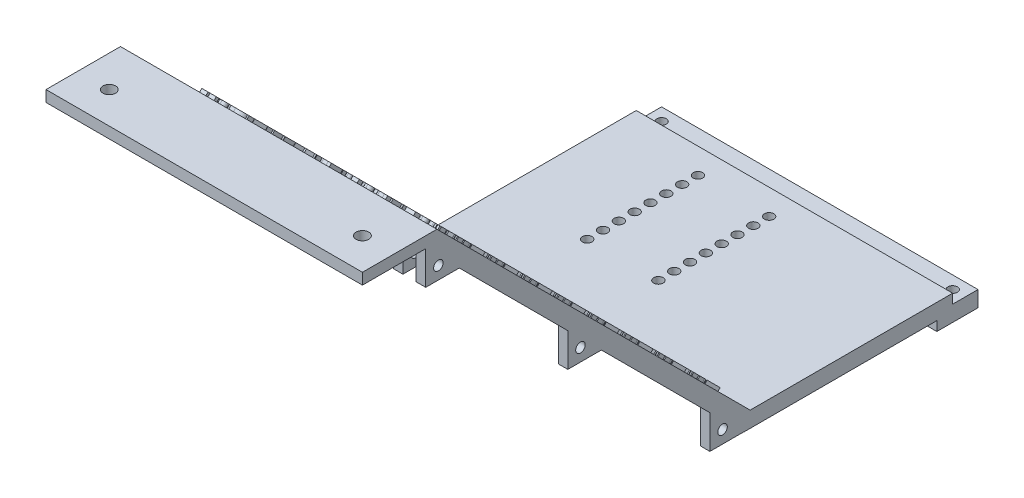
SolidWorks part; units mm, degrees
ref_plane "Front Plane" through (0, 0, 0) normal (0, 0, 1) x (1, 0, 0)
ref_plane "Top Plane" through (0, 0, 0) normal (0, 1, 0) x (1, 0, 0)
ref_plane "Right Plane" through (0, 0, 0) normal (1, 0, 0) x (0, 0, -1)
sketch "Sketch4" plane through (0, 0, 0) normal (1, 0, 0) x (0, 0, -1)
  line L0 (0, 0) -> (-8, 0)
  line L1 (-8, 0) -> (-8, 3)
  line L2 (-8, 3) -> (-72, 3)
  line L3 (-72, 3) -> (-170.9949, 101.9949)
  dimension "D1" = 8
  dimension "D2" = 3
  dimension "D3" = 64
  dimension "D4" = 135
  dimension "D5" = 140
extrude "Extrude-Thin2" add sketch "Sketch4" along normal blind 100 thin thin type one direction reverse wall 5
sketch "Sketch5" plane through (0, 3, 0) normal (0, 1, 0) x (1, 0, 0)
  line L1 (100, -8) -> (100, -72) construction
  line L2 (100, -8) -> (0, -8) construction
  circle A0 centre (50, -16) radius 1.5
  dimension "D2" = 3
  dimension "D1" = 50
  dimension "D3" = 8
extrude "Cut-Extrude1" cut sketch "Sketch5" against normal up to next
pattern_linear "LPattern1" count 8 spacing 5 along (0, 0, 1) count 2 spacing 22.5 along (-1, 0, 0) of "Cut-Extrude1"
sketch "Sketch7" plane through (100, 0, 0) normal (1, 0, 0) x (0, 0, -1)
  line L0 (-170.9949, 101.9949) -> (-174.5305, 101.9949)
  line L1 (-174.5305, 101.9949) -> (-174.5305, 98.4594)
  line L2 (-174.5305, 98.4594) -> (-170.9949, 101.9949)
extrude "Boss-Extrude1" add sketch "Sketch7" against normal up to surface (100 mm away) up to face at (0, 19.2454, 53.3597)
sketch "Sketch8" plane through (0, 0, 174.5305) normal (0, 0, 1) x (1, 0, 0)
  line L1 (0, 101.9949) -> (100, 101.9949)
  line L2 (0, 101.9949) -> (0, 98.4594)
  line L3 (0, 98.4594) -> (100, 98.4594)
  line L4 (100, 101.9949) -> (100, 98.4594)
extrude "Boss-Extrude2" add sketch "Sketch8" along normal blind 20
sketch "Sketch9" plane through (0, 101.9949, 0) normal (0, 1, 0) x (1, 0, 0)
  line L0 (100, -170.9949) -> (100, -194.5305) construction
  line L1 (100, -194.5305) -> (0, -194.5305) construction
  line L2 (0, -170.9949) -> (0, -194.5305) construction
  circle A0 centre (90, -184.5305) radius 2
  circle A1 centre (10, -184.5305) radius 2
  dimension "D1" = 4
  dimension "D2" = 4
  dimension "D3" = 10
  dimension "D4" = 10
  dimension "D5" = 10
  dimension "D6" = 10
extrude "Cut-Extrude2" cut sketch "Sketch9" against normal up to next
sketch "Sketch10" plane through (0, 0, 0) normal (0, 1, 0) x (1, 0, 0)
  line L0 (100, 0) -> (0, 0) construction
  line L1 (100, 0) -> (100, -8) construction
  line L2 (0, 0) -> (0, -8) construction
  circle A0 centre (4, -4) radius 1.5
  circle A1 centre (96, -4) radius 1.5
  dimension "D1" = 3
  dimension "D2" = 3
  dimension "D3" = 4
  dimension "D4" = 4
  dimension "D5" = 4
extrude "Cut-Extrude3" cut sketch "Sketch10" against normal up to next
sketch "Sketch11" plane through (100, 0, 0) normal (1, 0, 0) x (0, 0, -1)
  line L0 (-174.5305, 98.4594) -> (-174.5305, 87.8528)
  line L1 (-174.5305, 87.8528) -> (-163.9239, 87.8528)
  line L2 (-74.0711, -2) -> (-174.5305, 98.4594) construction
  line L3 (-174.5305, 98.4594) -> (-163.9239, 87.8528)
  dimension "D1" = 15
extrude "Boss-Extrude3" add sketch "Sketch11" against normal blind 3
sketch "Sketch12" plane through (100, 0, 0) normal (1, 0, 0) x (0, 0, -1)
  line L0 (-174.5305, 98.4594) -> (-174.5305, 87.8528) construction
  line L1 (-174.5305, 87.8528) -> (-163.9239, 87.8528) construction
  circle A0 centre (-170.5305, 91.8528) radius 1.5
  dimension "D1" = 3
  dimension "D2" = 4
  dimension "D3" = 4
extrude "Cut-Extrude4" cut sketch "Sketch12" against normal up to next
pattern_linear "LPattern2" count 3 spacing 63.5 along (0, -0.7071, -0.7071) count 2 spacing 97 along (-1, 0, 0) of "Boss-Extrude3", "Cut-Extrude4"
sketch "Sketch13" plane through (0, -2, 0) normal (0, -1, 0) x (1, 0, 0)
  line L0 (0, 13) -> (0, 74.0711) construction
  line L1 (0, 48.535) -> (3, 48.535)
  line L2 (0, 48.535) -> (0, 38.535)
  line L3 (0, 38.535) -> (3, 38.535)
  line L4 (3, 48.535) -> (3, 38.535)
  dimension "D1" = 3
  dimension "D2" = 10
  dimension "D3" = 25.535
extrude "Boss-Extrude4" add sketch "Sketch13" along normal blind 10
sketch "Sketch14" plane through (0, 0, 0) normal (-1, 0, 0) x (0, 0, 1)
  line L0 (38.535, -12) -> (38.535, -2) construction
  line L1 (48.535, -12) -> (38.535, -12) construction
  circle A0 centre (43.535, -7) radius 1.5
  dimension "D1" = 3
  dimension "D2" = 5
  dimension "D3" = 5
extrude "Cut-Extrude5" cut sketch "Sketch14" against normal up to next
sketch "Sketch15" plane through (0, -34.5, 34.5) normal (0, 0.7071, -0.7071) x (1, 0, 0)
  line L0 (100, -53.033) -> (100, -193.033) construction
  line L1 (100, -193.033) -> (0, -193.033) construction
  circle A0 centre (84, -176.233) radius 3.4
  circle A1 centre (84, -161.233) radius 3.4
  circle A2 centre (84, -146.233) radius 3.4
  circle A5 centre (84, -131.233) radius 3.4
  circle A6 centre (84, -116.233) radius 3.4
  circle A7 centre (84, -101.233) radius 3.4
  circle A8 centre (84, -86.233) radius 3.4
  circle A9 centre (84, -71.233) radius 3.4
  point P20 (0, 0)
  dimension "D1" = 6.8
  dimension "D2" = 6.8
  dimension "D3" = 6.8
  dimension "D8" = 6.8
  dimension "D9" = 6.8
  dimension "D10" = 6.8
  dimension "D11" = 6.8
  dimension "D16" = 6.8
  dimension "D4" = 16
  dimension "D5" = 16.8
  dimension "D6" = 15
  dimension "D7" = 15
  dimension "D12" = 15
  dimension "D13" = 15
  dimension "D14" = 15
  dimension "D15" = 15
  dimension "D17" = 15
extrude "Cut-Extrude6" cut sketch "Sketch15" against normal up to next
sketch "Sketch16" plane through (0, -34.5, 34.5) normal (0, 0.7071, -0.7071) x (1, 0, 0)
  circle A0 centre (59, -161.233) radius 3.4
  circle A1 centre (44, -161.233) radius 3.4
  circle A2 centre (29, -161.233) radius 3.4
  circle A3 centre (14, -161.233) radius 3.4
  circle A5 centre (84, -161.233) radius 3.4 construction
  circle A6 centre (66.5, -146.233) radius 3.4
  circle A7 centre (51.5, -146.233) radius 3.4
  circle A8 centre (36.5, -146.233) radius 3.4
  circle A9 centre (21.5, -146.233) radius 3.4
  circle A10 centre (6.5, -146.233) radius 3.4
  circle A12 centre (51.5, -131.233) radius 3.4
  circle A13 centre (36.5, -131.233) radius 3.4
  circle A14 centre (21.5, -131.233) radius 3.4
  dimension "D1" = 6.8
  dimension "D2" = 15
  dimension "D3" = 15
  dimension "D7" = 6.8
  dimension "D14" = 6.8
  dimension "D4" = 15
  dimension "D5" = 0
  dimension "D6" = 25
  dimension "D8" = 15
  dimension "D9" = 15
  dimension "D10" = 15
  dimension "D11" = 15
  dimension "D12" = 7.5
  dimension "D13" = 15
  dimension "D15" = 15
  dimension "D16" = 15
  dimension "D17" = 15
extrude "Cut-Extrude7" cut sketch "Sketch16" against normal up to next
sketch "Sketch17" plane through (0, -34.5, 34.5) normal (0, 0.7071, -0.7071) x (1, 0, 0)
  circle A0 centre (51.5, -111.233) radius 3.4
  circle A1 centre (36.5, -106.233) radius 3.4
  circle A2 centre (21.5, -111.233) radius 3.4
  circle A3 centre (36.5, -131.233) radius 3.4 construction
  circle A4 centre (84, -116.233) radius 3.4 construction
  dimension "D1" = 6.8
  dimension "D4" = 5
  dimension "D2" = 15
  dimension "D3" = 15
  dimension "D5" = 0
  dimension "D6" = 5
extrude "Cut-Extrude8" cut sketch "Sketch17" against normal up to next
pattern_linear "LPattern3" count 4 spacing 15 along (0, -0.7071, -0.7071) of "Cut-Extrude8"
ref_plane "Plane1" through (0, -34.5, 34.5) normal (0, 0.7071, -0.7071) x (-1, 0, 0)
sketch "Sketch19" plane through (0, -34.5, 34.5) normal (0, 0.7071, -0.7071) x (-1, 0, 0)
  circle A0 centre (-84, 176.233) radius 3.4 construction
  text T0 "SENDS" font "Century Gothic" height 5
  dimension "D1" = 10
  dimension "D2" = 8
extrude "Boss-Extrude5" add sketch "Sketch19" along normal blind 1
sketch "Sketch21" plane through (0, -34.5, 34.5) normal (0, 0.7071, -0.7071) x (-1, 0, 0)
  circle A0 centre (-59, 161.233) radius 3.4 construction
  circle A1 centre (-44, 161.233) radius 3.4 construction
  circle A2 centre (-29, 161.233) radius 3.4 construction
  circle A3 centre (-14, 161.233) radius 3.4 construction
  circle A4 centre (-36.5, 146.233) radius 3.4 construction
  circle A5 centre (-66.5, 146.233) radius 3.4 construction
  circle A6 centre (-51.5, 146.233) radius 3.4 construction
  circle A7 centre (-21.5, 146.233) radius 3.4 construction
  circle A8 centre (-6.5, 146.233) radius 3.4 construction
  circle A9 centre (-51.5, 131.233) radius 3.4 construction
  circle A10 centre (-36.5, 131.233) radius 3.4 construction
  circle A11 centre (-21.5, 131.233) radius 3.4 construction
  text T0 "DYANMICS\r\n" font "Century Gothic" height 5
  text T1 "THRESH"
  text T2 "ATK"
  text T3 "RLS"
  text T4 "KNEE"
  text T5 "THRESH"
  text T6 "ATK"
  text T7 "RLS"
  text T8 "KNEE"
  text T9 "RATIO" font "Century Gothic" height 3
  text T10 "THRESH"
  text T11 "ATK"
  text T12 "RLS"
  point P34 (0, 0)
  point P38 (0, 0)
  dimension "D1" = 8
  dimension "D2" = 4.25
  dimension "D3" = 4
  dimension "D4" = 6
  dimension "D5" = 20
  dimension "D6" = 8
  dimension "D7" = 5
  dimension "D8" = 5
  dimension "D9" = 4.25
  dimension "D10" = 4
  dimension "D11" = 6
  dimension "D12" = 6
  dimension "D13" = 12.5
  dimension "D14" = 8
  dimension "D15" = 5
  dimension "D16" = 4.25
  dimension "D17" = 4
extrude "Boss-Extrude6" add sketch "Sketch21" along normal blind 1
sketch "Sketch23" plane through (0, -34.5, 34.5) normal (0, 0.7071, -0.7071) x (-1, 0, 0)
  circle A0 centre (-51.5, 111.233) radius 3.4 construction
  circle A1 centre (-36.5, 106.233) radius 3.4 construction
  circle A2 centre (-21.5, 111.233) radius 3.4 construction
  text T0 "Q" font "Century Gothic" height 5
  text T1 "F" font "Century Gothic" height 5
  text T2 "G" font "Century Gothic" height 5
  text T3 "EQ" font "Century Gothic" height 5
  point P9 (0, 0)
  dimension "D1" = 2.7
  dimension "D2" = 6.5
  dimension "D3" = 6.5
  dimension "D4" = 2
  dimension "D5" = 2.7
  dimension "D6" = 4
  dimension "D7" = 7
extrude "Boss-Extrude7" add sketch "Sketch23" along normal blind 1
sketch "Sketch24" plane through (0, -34.5, 34.5) normal (0, 0.7071, -0.7071) x (-1, 0, 0)
  circle A0 centre (-84, 176.233) radius 3.4 construction
  circle A1 centre (-84, 161.233) radius 3.4 construction
  circle A2 centre (-84, 146.233) radius 3.4 construction
  circle A3 centre (-84, 131.233) radius 3.4 construction
  circle A4 centre (-84, 116.233) radius 3.4 construction
  circle A5 centre (-84, 101.233) radius 3.4 construction
  circle A6 centre (-84, 86.233) radius 3.4 construction
  circle A7 centre (-84, 71.233) radius 3.4 construction
  text T0 "AUX 1"
  text T1 "AUX 2"
  text T2 "AUX 3"
  text T3 "AUX 4"
  text T4 "AUX 5"
  text T5 "AUX 6"
  text T6 "AUX 7"
  text T7 "AUX 8"
  point P3 (0, 0)
  point P5 (-100, 167.4408)
  point P7 (0, 0)
  point P12 (0, 0)
  point P14 (0, 0)
  dimension "D1" = 9
  dimension "D2" = 12.5
  dimension "D3" = 9
  dimension "D4" = 9
  dimension "D5" = 9
  dimension "D6" = 9
  dimension "D7" = 9
  dimension "D8" = 9
  dimension "D9" = 9
extrude "Boss-Extrude8" add sketch "Sketch24" along normal blind 1
